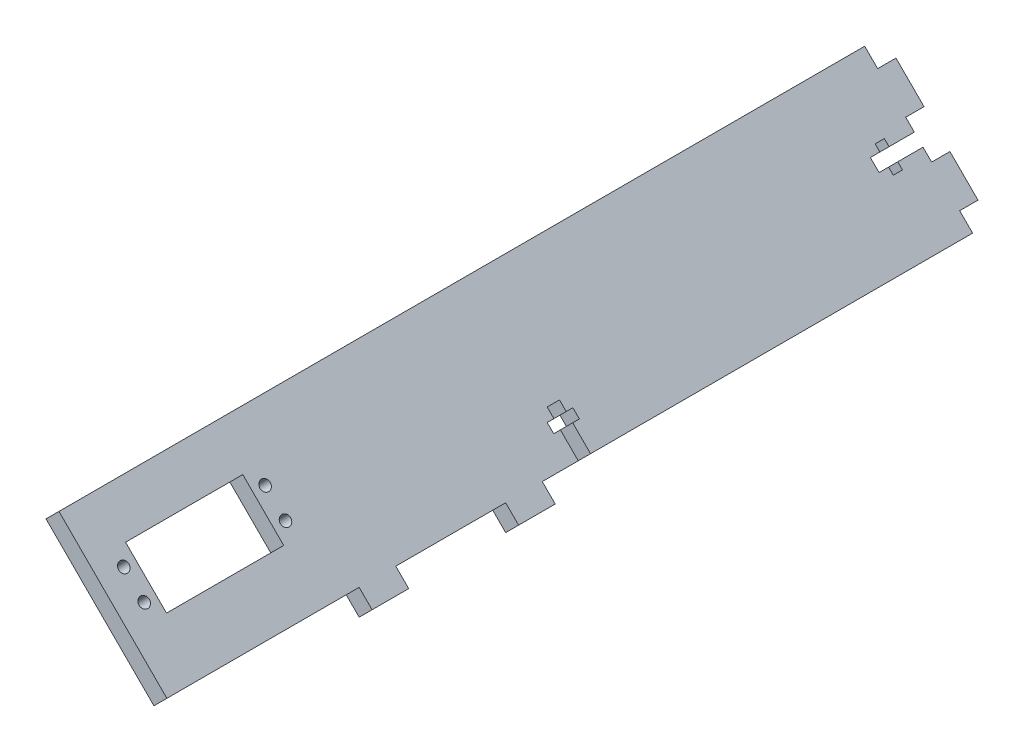
SolidWorks part; units mm, degrees
ref_plane "Front Plane" through (0, 0, 0) normal (0, 0, 1) x (1, 0, 0)
ref_plane "Top Plane" through (0, 0, 0) normal (0, 1, 0) x (1, 0, 0)
ref_plane "Right Plane" through (0, 0, 0) normal (1, 0, 0) x (0, 0, -1)
sketch "Sketch2" plane through (0, 0, 0) normal (0, 0, 1) x (1, 0, 0)
  line L0 (-71.1005, 3.7485) -> (-75.5906, -0.7416)
  line L1 (-71.1005, 3.7485) -> (-42.6562, -24.6957)
  line L2 (-75.5906, -0.7416) -> (-47.1463, -29.1858)
  line L3 (-42.6562, -24.6957) -> (-47.1463, -29.1858)
  line L4 (-75.5906, -0.7416) -> (-65.8586, -10.4736) construction
  line L5 (-61.3685, -5.9835) -> (-71.1005, 3.7485) construction
  line L6 (-47.1463, -29.1858) -> (-42.6562, -24.6957) construction
  line L7 (-71.1005, 3.7485) -> (-75.5906, -0.7416) construction
extrude "Base Extrusion" add sketch "Sketch2" along normal blind 279.4
sketch "Sketch3" plane through (-38.1661, -38.1661, 0) normal (-0.7071, -0.7071, 0) x (0, 0, 1)
  line L0 (0, 32.8131) -> (24.1393, 32.8131) construction
  line L1 (0, 52.9262) -> (0, 12.7) construction
  line B0 (0, 34.9467) -> (0, 30.6795)
  line B1 (11.938, 30.6795) -> (11.938, 28.3681)
  line B2 (11.938, 28.3681) -> (8.763, 28.3681)
  line B3 (8.763, 28.3681) -> (8.763, 30.6795)
  line B4 (8.763, 30.6795) -> (0, 30.6795)
  line B5 (11.938, 30.6795) -> (15.24, 30.6795)
  line B6 (15.24, 30.6795) -> (15.24, 34.9467)
  line B7 (11.938, 34.9467) -> (15.24, 34.9467)
  line B8 (8.763, 34.9467) -> (0, 34.9467)
  line B9 (8.763, 37.2581) -> (8.763, 34.9467)
  line B10 (11.938, 37.2581) -> (8.763, 37.2581)
  line B11 (11.938, 34.9467) -> (11.938, 37.2581)
sketch_block_instance "TSlot-1"
sketch_block "TSlot" parameters "D1"=3.302, "D2"=3.175
extrude "Base T Slot" cut sketch "Sketch3" against normal through all
sketch "Sketch4" plane through (0, 0, 0) normal (0, 0, -1) x (-1, 0, 0)
  line L0 (75.5906, -0.7416) -> (65.8586, -10.4736) construction
  line L1 (65.8586, -10.4736) -> (61.3685, -5.9835) construction
  line L2 (61.3685, -5.9835) -> (71.1005, 3.7485) construction
  line L3 (71.1005, 3.7485) -> (75.5906, -0.7416) construction
  line L4 (42.6562, -24.6957) -> (52.3882, -14.9637) construction
  line L5 (52.3882, -14.9637) -> (56.8783, -19.4538) construction
  line L6 (56.8783, -19.4538) -> (47.1463, -29.1858) construction
  line L7 (47.1463, -29.1858) -> (42.6562, -24.6957) construction
  line L8 (75.5906, -0.7416) -> (65.8586, -10.4736)
  line L9 (65.8586, -10.4736) -> (61.3685, -5.9835)
  line L10 (61.3685, -5.9835) -> (71.1005, 3.7485)
  line L11 (71.1005, 3.7485) -> (75.5906, -0.7416)
  line L12 (42.6562, -24.6957) -> (52.3882, -14.9637)
  line L13 (52.3882, -14.9637) -> (56.8783, -19.4538)
  line L14 (56.8783, -19.4538) -> (47.1463, -29.1858)
  line L15 (47.1463, -29.1858) -> (42.6562, -24.6957)
extrude "Base Tabs" add sketch "Sketch4" along normal blind 6.35
sketch "Sketch5" plane through (-33.676, -33.676, 0) normal (0.7071, 0.7071, 0) x (0, 0, -1)
  line L1 (-266.7, 44.5623) -> (-226.06, 44.5623)
  line L2 (-266.7, 44.5623) -> (-266.7, 24.4963)
  line L3 (-266.7, 24.4963) -> (-226.06, 24.4963)
  line L4 (-226.06, 44.5623) -> (-226.06, 24.4963)
  line L5 (-279.4, 12.7) -> (-279.4, 52.9262) construction
  line L8 (-165.1552, 44.5623) -> (-139.1365, 44.5623) construction
  line L9 (-139.1365, 24.4963) -> (-164.2745, 24.4963) construction
  dimension "D1" = 40.64
  dimension "D2" = 12.7
  dimension "D3" = 20.066
extrude "Servo Slot" cut sketch "Sketch5" against normal through all
sketch "Sketch6" plane through (-33.676, -33.676, 0) normal (0.7071, 0.7071, 0) x (0, 0, -1)
  line L0 (-183.9541, 34.5293) -> (-125.6675, 34.5293) construction
  line L14 (-266.7, 44.5623) -> (-266.7, 24.4963) construction
  arc A0 (-272.1243, 38.2593) -> (-272.1243, 40.7993) centre (-270.88, 39.5293) ccw construction
  arc A1 (-220.6357, 40.7993) -> (-220.6357, 38.2593) centre (-221.88, 39.5293) ccw construction
  circle A8 centre (-270.88, 39.5293) radius 1.778
  circle A9 centre (-270.88, 29.5293) radius 1.778
  circle A10 centre (-221.88, 39.5293) radius 1.778
  circle A11 centre (-221.88, 29.5293) radius 1.778
  point P26 (-266.7, 34.5293)
extrude "Servo Mounting Holes" cut sketch "Sketch6" against normal through all
sketch "Sketch7" plane through (0, 0, 279.4) normal (0, 0, 1) x (1, 0, 0)
  line L0 (-47.1463, -29.1858) -> (-42.6562, -24.6957)
  line L1 (-47.1463, -29.1858) -> (-42.6562, -33.676)
  line L2 (-42.6562, -24.6957) -> (-38.1661, -29.1858)
  line L3 (-42.6562, -33.676) -> (-38.1661, -29.1858)
  line L4 (-92.784, -83.8038) -> (-85.6806, -76.7004) construction
  line L5 (-75.5906, -0.7416) -> (-71.1005, 3.7485)
  line L6 (-75.5906, -0.7416) -> (-80.0807, 3.7485)
  line L7 (-71.1005, 3.7485) -> (-75.5906, 8.2387)
  line L8 (-80.0807, 3.7485) -> (-75.5906, 8.2387)
extrude "Filler Extrusion to Funnel Support" add sketch "Sketch7" against normal up to surface (279.4 mm away)
sketch "Sketch8" plane through (-33.676, -33.676, 0) normal (0.7071, 0.7071, 0) x (0.7071, -0.7071, 0)
  line L0 (28.1183, -134.62) -> (-82.975, -134.62) construction
  line L3 (-6.35, -279.4) -> (-6.35, -212.725) construction
  line B0 (-6.35, -136.7536) -> (-6.35, -132.4864)
  line B1 (-18.288, -132.4864) -> (-18.288, -130.175)
  line B2 (-18.288, -130.175) -> (-15.113, -130.175)
  line B3 (-15.113, -130.175) -> (-15.113, -132.4864)
  line B4 (-15.113, -132.4864) -> (-6.35, -132.4864)
  line B5 (-18.288, -132.4864) -> (-21.59, -132.4864)
  line B6 (-21.59, -132.4864) -> (-21.59, -136.7536)
  line B7 (-18.288, -136.7536) -> (-21.59, -136.7536)
  line B8 (-15.113, -136.7536) -> (-6.35, -136.7536)
  line B9 (-15.113, -139.065) -> (-15.113, -136.7536)
  line B10 (-18.288, -139.065) -> (-15.113, -139.065)
  line B11 (-18.288, -136.7536) -> (-18.288, -139.065)
sketch_block_instance "TSlot-2"
extrude "Side T Slot" cut sketch "Sketch8" against normal through all
sketch "Sketch9" plane through (-4.4901, 4.4901, 0) normal (0.7071, -0.7071, 0) x (-0.7071, -0.7071, 0)
  line L0 (49.5253, -247.9715) -> (49.5253, -199.7444) construction
  line L1 (53.975, -136.7536) -> (53.975, -279.4) construction
  line L2 (53.975, -212.725) -> (47.625, -212.725)
  line L3 (53.975, -212.725) -> (53.975, -200.025)
  line L4 (53.975, -200.025) -> (47.625, -200.025)
  line L5 (47.625, -212.725) -> (47.625, -200.025)
  line L6 (47.625, -136.7536) -> (47.625, -279.4) construction
  line L7 (53.975, 0) -> (53.975, -132.4864) construction
  line L8 (53.975, -161.925) -> (47.625, -161.925)
  line L9 (53.975, -161.925) -> (53.975, -149.225)
  line L10 (53.975, -149.225) -> (47.625, -149.225)
  line L11 (47.625, -161.925) -> (47.625, -149.225)
  line L12 (47.625, 0) -> (47.625, -132.4864) construction
  line L13 (104.7498, -180.975) -> (30.8469, -180.975) construction
  line L14 (53.975, -279.4) -> (47.625, -279.4) construction
  line L15 (29.2312, -82.55) -> (47.625, -82.55) construction
  dimension "D1" = 12.7
  dimension "D2" = 19.05
extrude "Side Tabs" add sketch "Sketch9" along normal up to surface (6.35 mm away)
